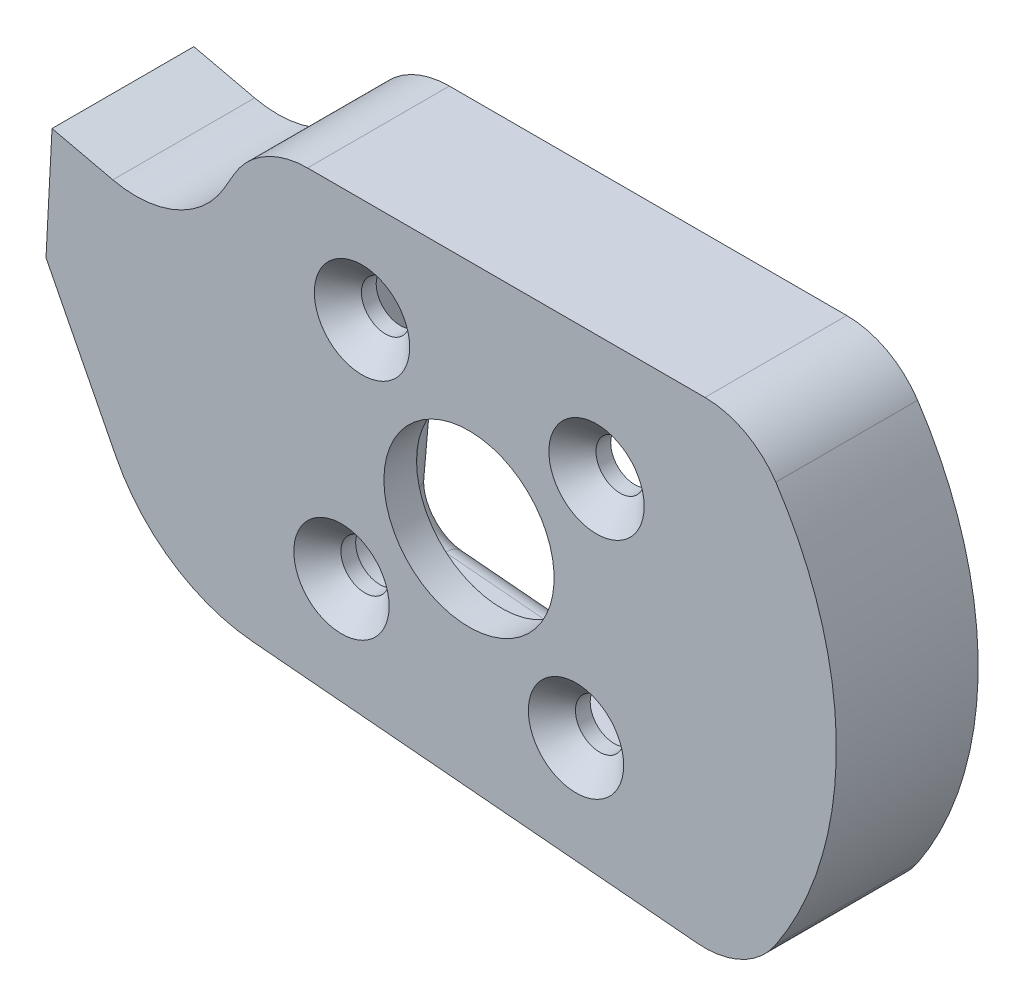
SolidWorks part; units mm, degrees
material "AISI 4340 Aço, normalizado"
ref_plane "Plano frontal" through (0, 0, 0) normal (0, 0, 1) x (1, 0, 0)
ref_plane "Plano superior" through (0, 0, 0) normal (0, 1, 0) x (1, 0, 0)
ref_plane "Plano direito" through (0, 0, 0) normal (1, 0, 0) x (0, 0, -1)
other "Center of Mass"
sketch "Sketch2" plane through (0, 0, 0) normal (0, 0, 1) x (1, 0, 0)
  line L0 (0, 0) -> (-50, 0) construction
  line L1 (-127.5781, 46.0511) -> (-149.0143, 51)
  line L2 (0, 0) -> (-155.9672, 21.9198) construction
  line L5 (-58.9322, 84) -> (81.1804, 84)
  line L6 (0, 0) -> (0, 41.2714) construction
  line L8 (-84.913, 69) -> (-88.303, 63.1284)
  line L14 (-78.3219, -70.2808) -> (78.4896, -84)
  line L19 (-149.0143, 51) -> (-151.1368, 10.5)
  line L20 (-149.5248, 48.7888) -> (-147.8193, 56.1762) construction
  line L22 (-151.1368, 10.5) -> (-126.5529, -37.7485)
  circle A0 centre (0, 0) radius 157.5 construction
  arc A5 (81.1804, 84) -> (106.1589, 70.6154) centre (81.1804, 54) cw
  arc A6 (-58.9322, 84) -> (-84.913, 69) centre (-58.9322, 54) ccw
  arc A17 (-126.5529, -37.7485) -> (-78.3219, -70.2808) centre (-73.0925, -10.5091) ccw
  arc A18 (-127.5781, 46.0511) -> (-88.303, 63.1284) centre (-119.4799, 81.1284) ccw
  arc A20 (106.1589, 70.6154) -> (106.0595, -70.7647) centre (0, 0) cw
  arc A21 (78.4896, -84) -> (106.0595, -70.7647) centre (81.1043, -54.1142) ccw
  point P29 (-157.5, 0)
  point P31 (29.3939, 84)
  point P32 (-76.2527, 84)
  point P33 (106.1589, -70.6154)
  dimension "D1" = 315
  dimension "D4" = 30
  dimension "D5" = 36
  dimension "D13" = 30
  dimension "D11" = 60
  dimension "D10" = 84
  dimension "D2" = 5
  dimension "D3" = 10
  dimension "D7" = 30
  dimension "D8" = 77
  dimension "D12" = 30
  dimension "D9" = 51
  dimension "D14" = 40.5
  dimension "D15" = 22
  dimension "D6" = 30
  dimension "D16" = 5
  dimension "D17" = 84
extrude "EXTRUSÃO PRINCIPAL" add sketch "Sketch2" along normal blind 50 contours L5 A5 A20 A21 L14 A17 L22 L19 L1 A18 L8 A6
other "Ponto de referência do centro da massa1"
ref_plane "Plano2" through (0, 2.2662, 0) normal (0, -1, 0) x (-1, 0, 0)
ref_plane "Plano3" through (-2.0065, 0, 0) normal (1, 0, 0) x (0, 0, -1)
sketch "Esboço2" plane through (0, 0, 0) normal (0, 0, -1) x (-1, 0, 0)
  line L0 (-8.25, 2.2662) -> (8.25, 2.2662) construction
  line L1 (-48.3318, 55.5818) -> (42.3219, 63.513)
  line L2 (-59.2402, 42.5816) -> (-51.3091, -48.0721)
  line L3 (-38.3089, -58.9806) -> (52.3449, -51.0494)
  line L4 (55.3221, 52.6045) -> (63.2533, -38.0492)
  line L5 (-60.2861, 54.5359) -> (64.2992, -50.0035) construction
  line L6 (-50.2632, -60.0265) -> (54.2763, 64.5588) construction
  line L7 (2.0065, 8.25) -> (2.0065, -8.25) construction
  line L8 (78.3219, -70.2808) -> (-78.4896, -84) construction
  line L10 (2.503, 2.2662) -> (86.0271, 2.2662) construction
  circle A0 centre (2.0065, 2.2662) radius 30
  arc A2 (-48.3318, 55.5818) -> (-59.2402, 42.5816) centre (-47.2859, 43.6275) ccw
  arc A3 (42.3219, 63.513) -> (55.3221, 52.6045) centre (43.3678, 51.5586) cw
  arc A4 (52.3449, -51.0494) -> (63.2533, -38.0492) centre (51.299, -39.0951) ccw
  arc A5 (-51.3091, -48.0721) -> (-38.3089, -58.9806) centre (-39.3547, -47.0263) ccw
  circle A6 centre (2.0065, 2.2662) radius 42.5
  circle A7 centre (2.0065, 2.2662) radius 37.5
  circle A8 centre (2.0065, 2.2662) radius 27 construction
  dimension "D1" = 12
  dimension "D5" = 85
  dimension "D6" = 75
  dimension "D7" = 54
  dimension "D3" = 115
  dimension "D4" = 115
  dimension "D2" = 3
extrude "REBAIXO CAMISA" cut sketch "Esboço2" against normal blind 36.5 contours L1 A3 L4 A4 L3 A5 L2 A2
fillet "FILETE ALIVIO REBAIXO" radius 8 8 edges at (56.4784, 51.3409, 0) (55.2747, -2.7453, 0) (47.0682, -56.2188, 0) (-7.018, -55.015, 0) (-60.4915, -46.8085, 0) (-59.2877, 7.2776, 0) (-51.0813, 60.7512, 0) (3.0049, 59.5474, 0)
extrude "FURO EIXO" cut sketch "Esboço2<3>" against normal through all contours A0
sketch "Esboço2<3>" plane through (0, 0, 0) normal (0, 0, -1) x (-1, 0, 0) same geometry as "Esboço2"
extrude "Corte-extrusão1" cut sketch "Esboço2<4>" against normal blind 2 from surface contours A7 starting at face at (-32.0065, 2.2662, 36.5)
sketch "Esboço2<4>" plane through (0, 0, 0) normal (0, 0, -1) x (-1, 0, 0) same geometry as "Esboço2"
sketch "Esboço3" plane through (0, 0, 50) normal (0, 0, 1) x (1, 0, 0)
  line L0 (-78.3219, -70.2808) -> (78.4896, -84) construction
  line L1 (-46.9656, -35.4589) -> (35.7186, -42.6929) construction
  line L2 (-46.9656, -35.4589) -> (-39.7317, 47.2252) construction
  line L3 (-39.7317, 47.2252) -> (42.9525, 39.9913) construction
  line L4 (35.7186, -42.6929) -> (42.9525, 39.9913) construction
  line L5 (-46.9656, -35.4589) -> (42.9525, 39.9913) construction
  line L6 (-39.7317, 47.2252) -> (35.7186, -42.6929) construction
  circle A0 centre (-2.0065, 2.2662) radius 30 construction
  point P0 (-2.0065, 2.2662)
  dimension "D1" = 83
hole_wizard "Escareado para parafuso Allen sextavado escareado de M161" positions "Esboço4" profile "Esboço7" countersink size "M16" standard "ISO" end condition through all
sketch "Esboço4" plane through (0, 0, 50) normal (0, 0, 1) x (1, 0, 0)
  point P0 (-39.7317, 47.2252)
  point P3 (42.9525, 39.9913)
  point P6 (-46.9656, -35.4589)
  point P9 (35.7186, -42.6929)
sketch "Esboço7" plane through (-39.7317, 47.2252, 50) normal (1, 0, 0) x (0, -1, 0)
  line L0 (0, 0) -> (0, 50)
  line L1 (0, 50) -> (8.5, 50)
  line L2 (8.5, 50) -> (8.5, 8.3)
  line L3 (8.5, 8.3) -> (16.8, 0)
  line L5 (16.8, 0) -> (0, 0)
  line L6 (-8.5, 8.3) -> (-16.8, 0) construction
  line L11 (0, -6.35) -> (0, 107.95) construction
  dimension "Thru Hole Dia." = 17
  dimension "Thru Hole Depth" = 50
  dimension "Near C'Sink Dia." = 33.6
  dimension "Near C'Sink Angle" = 90
chamfer "CHANFRO CAMISA" [suppressed] distance 1 angle 45
sketch "REF. POLIA" plane through (0, 0, 0) normal (0, 0, -1) x (-1, 0, 0)
  circle A0 centre (1.8584, 2.135) radius 71
  circle A1 centre (1.8584, 2.135) radius 30 construction
  dimension "D1" = 142
equation "\"escala\"= 1                        'projeto - escala geral"
equation "\"escala_disco-arma\"= 3                                                                  'disco arma - escala geometria disco arma"
equation "\"rolamento_D-ext\"= 85               'rolamento arma - diametro externo"
equation "\"rolamento_d-int\"= 45               'rolamento arma - diametro interno"
equation "\"rolamento_b-esp\"= 23               'rolamento arma - espessura"
equation "\"arma_rebaixo-camisa_b\"= \"rolamento_b-esp\" + (\"arma-espessura\"-\"rolamento_b-esp\")/2     'disco arma - profundidade rebaixo camisa"
equation "\"arma-espessura\"= 50                                                                    'disco arma - espessura disco arma"
equation "\"D1@EXTRUSÃO PRINCIPAL\" = \"arma-espessura\""
equation "\"eixo_diam\"= \"rolamento_d-int\"      'eixo arma - diametro"
equation "\"camisa_largura\"=115                                                        'camisa arma - tamanho do lado"
equation "\"D3@Esboço2\"=\"camisa_largura\""
equation "\"camisa_raio\"= 16                                                           'camisa arma - raio canto interno"
equation "\"arma_rebaixo-camisa_raio\"= 12                                                         'disco arma - raio do rebaixo da camisa da arma "
equation "\"D1@Esboço2\"=\"arma_rebaixo-camisa_raio\""
equation "\"arma_alivio_raio\"= 12 * \"escala_disco-arma\""
equation "\"arma_diam_max\"= 105 * \"escala_disco-arma\""
equation "\"D1@Sketch2\" = \"arma_diam_max\""
equation "\"arma_arestas_raio\"= 10 * \"escala_disco-arma\""
equation "\"D4@Sketch2\" = \"arma_arestas_raio\""
equation "\"arma_altura_superior-centro\"= 28 * \"escala_disco-arma\""
equation "\"D10@Sketch2\" = \"arma_altura_superior-centro\""
equation "\"arma_dente_raio\"= 12 * \"escala_disco-arma\""
equation "\"D5@Sketch2\" = \"arma_dente_raio\""
equation "\"arma_altura_dente-centro\"= 17 * \"escala_disco-arma\""
equation "\"D9@Sketch2\"=\"arma_altura_dente-centro\""
equation "\"arma_dente_altura\"= 13.5 * \"escala_disco-arma\""
equation "\"arma_alivio-dente_raio\"= 20 * \"escala_disco-arma\""
equation "\"arma_traseira_offset\"= 10 * \"escala_disco-arma\""
equation "\"arma_centralizacao_offset\"= 8 * \"escala_disco-arma\""
equation "\"arma_eixo-furo_folga\"= 4                                                              'disco arma - folga entre furo arma e eixo"
equation "\"D1@REBAIXO CAMISA\" = \"arma_rebaixo-camisa_b\""
equation "\"D6@Sketch2\"=\"arma_traseira_offset\""
equation "\"D11@Sketch2\"=\"arma_alivio-dente_raio\""
equation "\"D4@Esboço2\"=\"camisa_largura\""
equation "\"D14@Sketch2\"=\"arma_dente_altura\""
equation "\"arma_altura_inferior-centro\"= 28 * \"escala_disco-arma\""
equation "\"D17@Sketch2\"=\"arma_altura_inferior-centro\""
equation "\"D13@Sketch2\"=\"arma_arestas_raio\""
equation "\"D5@Esboço2\"=\"rolamento_D-ext\""
equation "\"polia_diam_eff\"= 142"
equation "\"D1@REF. POLIA\" = \"polia_diam_eff\""
equation "\"arma_dente_comprimento\"=22"
equation "\"D15@Sketch2\"=\"arma_dente_comprimento\""
equation "\"camisa_rebaixo_rolamento\"= 1 * \"rolamento_b-esp\""
equation "\"polia_espessura\"= 40  "
equation "\"rolamento_D1-ext\"= 75             'rolamento arma - ressalto diam externo"
equation "\"rolamenot_d2-int\"= 54             'rolamento arma - ressalto diam interno"
equation "\"camisa_raio-alivio\"= 6                                                    'camisa arma - raio de alivio de tensoes no encaixe da arma"
equation "\"camisa_comprimento-centro\"= 2*(\"arma_rebaixo-camisa_b\")+\"polia_espessura\" "
equation "\"camisa_furos_dist\"= 83"
equation "\"camisa_furos_prof\"= 30"
equation "\"D1@FILETE ALIVIO REBAIXO\" = \"camisa_raio-alivio\" + 2"
equation "\"D6@Esboço2\"=\"rolamento_D1-ext\""
equation "\"D7@Esboço2\"=\"rolamenot_d2-int\""
equation "\"D1@Esboço3\"=\"camisa_furos_dist\""
